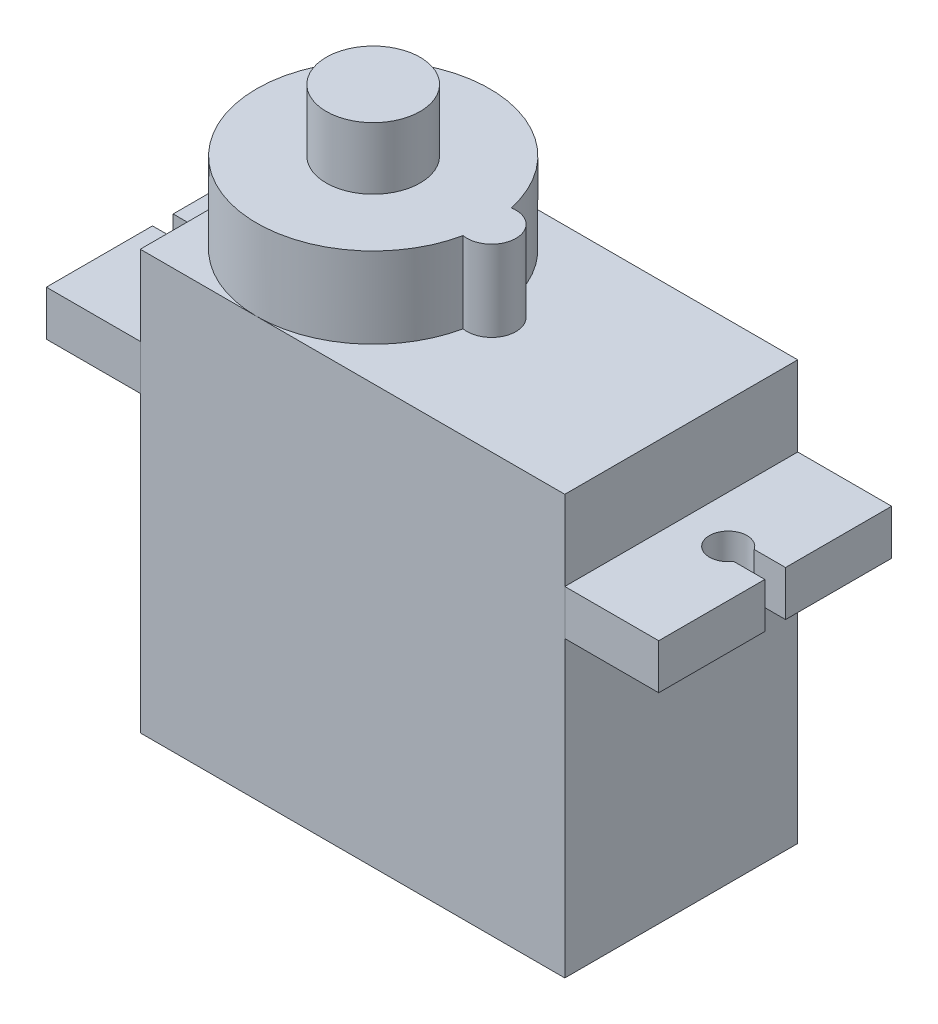
SolidWorks part; units mm, degrees
ref_plane "Front Plane" through (0, 0, 0) normal (0, 0, 1) x (1, 0, 0)
ref_plane "Top Plane" through (0, 0, 0) normal (0, 1, 0) x (1, 0, 0)
ref_plane "Right Plane" through (0, 0, 0) normal (1, 0, 0) x (0, 0, -1)
sketch "Sketch1" plane through (0, 0, 0) normal (0, 1, 0) x (1, 0, 0)
  line L1 (-11.3, -6.2) -> (11.3, -6.2)
  line L2 (-11.3, -6.2) -> (-11.3, 6.2)
  line L3 (-11.3, 6.2) -> (11.3, 6.2)
  line L4 (11.3, -6.2) -> (11.3, 6.2)
  line L5 (-11.3, -6.2) -> (11.3, 6.2) construction
  line L6 (-11.3, 6.2) -> (11.3, -6.2) construction
  point P0 (0, 0)
  dimension "D1" = 22.6
  dimension "D2" = 12.4
extrude "Boss-Extrude1" add sketch "Sketch1" along normal blind 22.3
sketch "Sketch2" plane through (11.3, 0, 0) normal (1, 0, 0) x (0, 0, -1)
  line L0 (-6.2, 22.3) -> (-6.2, 0) construction
  line L1 (-6.2, 18.05) -> (6.2, 18.05)
  line L2 (-6.2, 18.05) -> (-6.2, 15.65)
  line L3 (-6.2, 15.65) -> (6.2, 15.65)
  line L4 (6.2, 18.05) -> (6.2, 15.65)
  line L5 (6.2, 22.3) -> (6.2, 0) construction
  line L6 (-6.2, 22.3) -> (6.2, 22.3) construction
  dimension "D1" = 4.25
  dimension "D2" = 2.4
extrude "Boss-Extrude2" add sketch "Sketch2" along normal blind 5 separate body
sketch "Sketch3" plane through (-11.3, 0, 0) normal (-1, 0, 0) x (0, 0, 1)
  line L4 (6.2, 15.65) -> (6.2, 18.05)
  line L5 (-6.2, 15.65) -> (6.2, 15.65)
  line L6 (-6.2, 18.05) -> (-6.2, 15.65)
  line L7 (6.2, 18.05) -> (-6.2, 18.05)
  line L8 (6.2, 15.65) -> (6.2, 18.05)
  line L9 (-6.2, 15.65) -> (6.2, 15.65)
  line L10 (-6.2, 18.05) -> (-6.2, 15.65)
  line L11 (6.2, 18.05) -> (-6.2, 18.05)
  dimension "D1" = 0
extrude "Boss-Extrude3" add sketch "Sketch3" along normal blind 5 separate body
sketch "Sketch4" plane through (0, 18.05, 0) normal (0, 1, 0) x (1, 0, 0)
  line L0 (-16.3, -6.2) -> (-16.3, 6.2) construction
  line L1 (16.3, 6.2) -> (16.3, -6.2) construction
  line L3 (-16.3, 0.55) -> (-14.6352, 0.55)
  line L4 (-16.3, 0.55) -> (-16.3, -0.55)
  line L5 (-16.3, -0.55) -> (-14.6352, -0.55)
  line L7 (16.3, -0.55) -> (14.6352, -0.55)
  line L8 (16.3, -0.55) -> (16.3, 0.55)
  line L9 (16.3, 0.55) -> (14.6352, 0.55)
  arc A0 (-14.6352, -0.55) -> (-14.6352, 0.55) centre (-13.8, 0) ccw
  arc A1 (14.6352, 0.55) -> (14.6352, -0.55) centre (13.8, 0) ccw
  dimension "D1" = 2
  dimension "D2" = 2
  dimension "D4" = 2.5
  dimension "D3" = 2.5
  dimension "D5" = 1.1
  dimension "D6" = 0.55
  dimension "D7" = 1.1
  dimension "D8" = 0.55
extrude "Cut-Extrude1" cut sketch "Sketch4" against normal up to next (2.4 mm away)
sketch "Sketch5" plane through (0, 18.05, 0) normal (0, 1, 0) x (1, 0, 0)
  line L0 (16.3, 6.2) -> (16.3, -6.2) construction
  line L1 (14.6352, 0.55) -> (16.3, 0.55)
  line L3 (14.6352, -0.55) -> (16.3, -0.55)
  line L4 (16.3, 0.55) -> (16.3, -0.55)
  arc A0 (14.6352, 0.55) -> (14.6352, -0.55) centre (13.8, 0) ccw
  dimension "D1" = 2
  dimension "D2" = 1.1
  dimension "D3" = 0.55
  dimension "D4" = 2.5
extrude "Cut-Extrude2" cut sketch "Sketch5" against normal up to next (2.4 mm away) contours L1 L4 L3 A0
sketch "Sketch6" plane through (0, 22.3, 0) normal (0, 1, 0) x (1, 0, 0)
  line L0 (-11.3, 6.2) -> (-11.3, -6.2) construction
  line L1 (1.2, 1.3) -> (0.9622, 1.3)
  line L2 (1.2, -1.3) -> (0.9622, -1.3)
  arc A0 (0.9667, 1.2789) -> (0.9667, -1.2789) centre (-5.1, 0) ccw
  arc A1 (0.9667, -1.2789) -> (0.9667, 1.2789) centre (1.2, 0) ccw
  dimension "D2" = 12.4
  dimension "D3" = 2.6
  dimension "D1" = 6.2
  dimension "D4" = 6.3
extrude "Boss-Extrude4" add sketch "Sketch6" along normal blind 4.3 contours A1 A0 region at (-4.9342, 22.3, 0)
sketch "Sketch7" plane through (0, 26.6, 0) normal (0, 1, 0) x (1, 0, 0)
  circle A0 centre (-5.1, 0) radius 2.5
  dimension "D1" = 5
extrude "Boss-Extrude5" add sketch "Sketch7" along normal blind 3.3
sketch "Sketch8" plane through (-11.3, 0, 0) normal (-1, 0, 0) x (0, 0, 1)
  line L0 (-6.2, 0) -> (6.2, 0) construction
  circle A0 centre (-1.2, 4.5) radius 0.6
  circle A1 centre (0, 4.5) radius 0.6
  circle A2 centre (1.2, 4.5) radius 0.6
  dimension "D1" = 4.5
  dimension "D2" = 1.2
  dimension "D3" = 1.2
  dimension "D4" = 1.2
extrude "Boss-Extrude7" add sketch "Sketch8" along normal blind 2.3 separate body contours A1 | A0 | A2 region at (-11.3, 4.5, -1.2) region at (-11.3, 4.5, 1.2) region at (-11.3, 4.5, 0)
